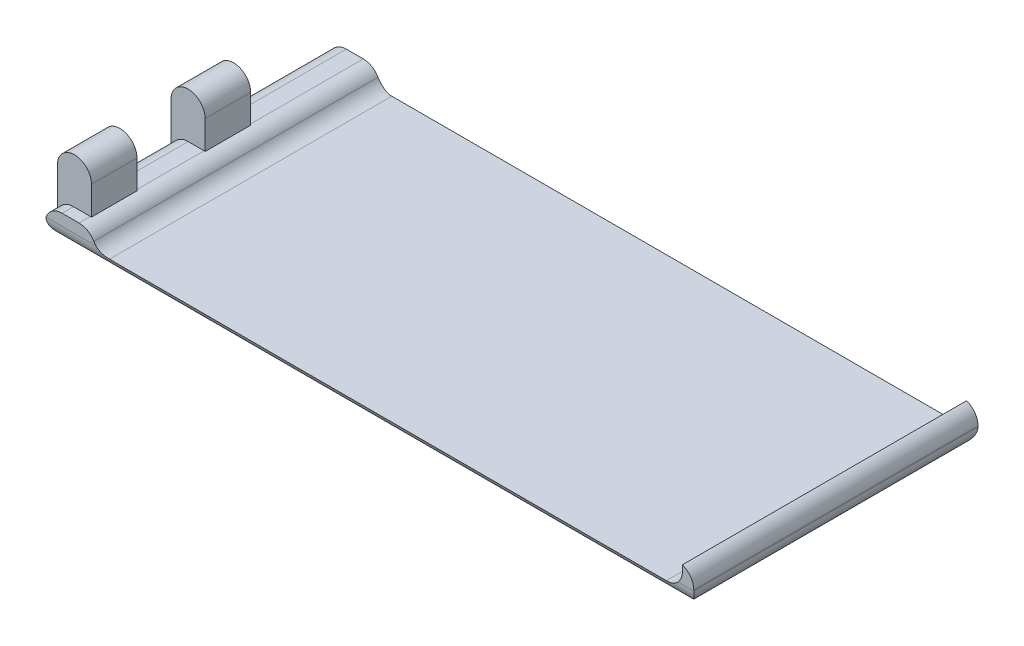
SolidWorks part; units mm, degrees
ref_plane "Front Plane" through (0, 0, 0) normal (0, 0, 1) x (1, 0, 0)
ref_plane "Top Plane" through (0, 0, 0) normal (0, 1, 0) x (1, 0, 0)
ref_plane "Right Plane" through (0, 0, 0) normal (1, 0, 0) x (0, 0, -1)
sketch "Sketch1" plane through (0, 0, 0) normal (0, 1, 0) x (1, 0, 0)
  line L1 (-56.975, 25) -> (56.975, 25)
  line L2 (-56.975, 25) -> (-56.975, -25)
  line L3 (-56.975, -25) -> (56.975, -25)
  line L4 (56.975, 25) -> (56.975, -25)
  line L5 (-56.975, 25) -> (56.975, -25) construction
  line L6 (-56.975, -25) -> (56.975, 25) construction
  point P0 (0, 0)
  dimension "D1" = 113.95
  dimension "D2" = 50
extrude "Boss-Extrude1" add sketch "Sketch1" along normal blind 2
sketch "Sketch2" plane through (0, 2, 0) normal (0, 1, 0) x (1, 0, 0)
  line L5 (-56.975, 25) -> (-48.975, 25)
  line L6 (-56.975, 25) -> (-56.975, -25)
  line L7 (-56.975, -25) -> (-48.975, -25)
  line L8 (-48.975, 25) -> (-48.975, -25)
  dimension "D1" = 50
  dimension "D2" = 8
extrude "Boss-Extrude2" add sketch "Sketch2" along normal blind 3
sketch "Sketch3" plane through (0, 2, 0) normal (0, 1, 0) x (1, 0, 0)
  line L0 (-48.975, -25) -> (56.975, -25) construction
  line L1 (56.975, 25) -> (54.975, 25)
  line L2 (56.975, 25) -> (56.975, -25)
  line L3 (56.975, -25) -> (54.975, -25)
  line L4 (54.975, 25) -> (54.975, -25)
  dimension "D1" = 50
  dimension "D2" = 2
extrude "Boss-Extrude3" add sketch "Sketch3" along normal blind 4
sketch "Sketch7" plane through (0, 5, 0) normal (0, 1, 0) x (1, 0, 0)
  line L0 (-48.975, -25) -> (-48.975, 25) construction
  line L1 (-56.975, 5) -> (-50.975, 5)
  line L2 (-56.975, 5) -> (-56.975, -3)
  line L3 (-56.975, -3) -> (-50.975, -3)
  line L4 (-50.975, 5) -> (-50.975, -3)
  line L5 (-48.975, 25) -> (-56.975, 25) construction
  dimension "D1" = 8
  dimension "D2" = 6
  dimension "D3" = 2
  dimension "D4" = 20
extrude "Boss-Extrude5" add sketch "Sketch7" along normal blind 8
fillet "Fillet1" 2 edges at (-50.975, 13, -1) (-56.975, 13, -1) type full round first side face at (-50.975, 9, -1) second side face at (-56.975, 5.75, -0.5) middle face at (-53.975, 13, -1)
sketch "Sketch10" plane through (0, 0, -5) normal (0, 0, -1) x (-1, 0, 0)
  circle A0 centre (53.975, 10) radius 1.525
  arc A1 (56.975, 10) -> (50.975, 10) centre (53.975, 10) ccw construction
  dimension "D1" = 3.05
extrude "Cut-Extrude2" cut sketch "Sketch10" against normal blind 2
pattern_linear "LPattern2" count 2 spacing 20 along (0, 0, 1) of "Cut-Extrude2", "Fillet1", "Boss-Extrude5"
fillet "Fillet2" radius 3 4 edges at (0, 0, -25) (-56.975, 0, 0) (0, 0, 25) (56.975, 0, 0)
fillet "Fillet3" radius 3 2 edges at (-48.975, 2, 0) (54.975, 2, 0)
fillet "Fillet4" radius 3 4 edges at (-48.975, 5, 0) (-56.975, 5, 9) (-56.975, 5, -15) (-56.975, 5, 24)
fillet "Fillet5" radius 3 1 edges at (56.975, 6, 0)
